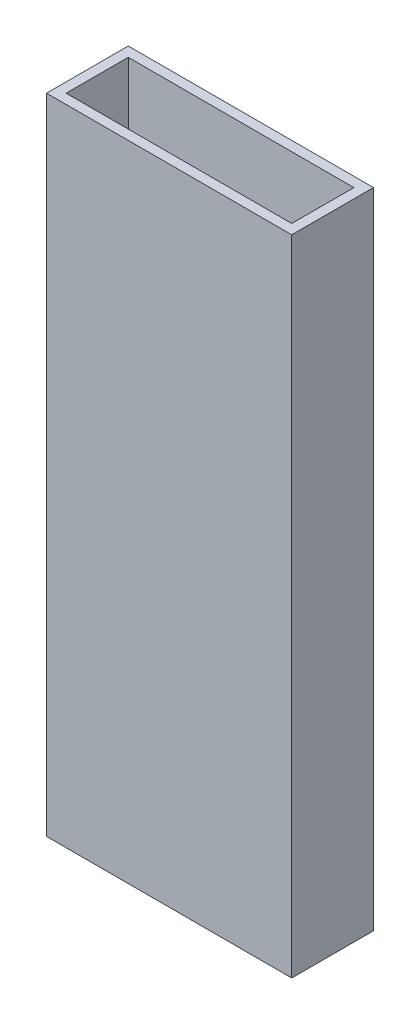
SolidWorks part; units mm, degrees
ref_plane "Front Plane" through (0, 0, 0) normal (0, 0, 1) x (1, 0, 0)
ref_plane "Top Plane" through (0, 0, 0) normal (0, 1, 0) x (1, 0, 0)
ref_plane "Right Plane" through (0, 0, 0) normal (1, 0, 0) x (0, 0, -1)
sketch "Sketch1" plane through (0, 0, 0) normal (0, 1, 0) x (1, 0, 0)
  line L0 (0, 9.652) -> (0, 12.7) construction
  line L1 (-38.1, 12.7) -> (38.1, 12.7)
  line L2 (-38.1, 12.7) -> (-38.1, -12.7)
  line L3 (-38.1, -12.7) -> (38.1, -12.7)
  line L4 (38.1, 12.7) -> (38.1, -12.7)
  line L5 (-35.052, 9.652) -> (35.052, 9.652)
  line L6 (-35.052, 9.652) -> (-35.052, -9.652)
  line L7 (-35.052, -9.652) -> (35.052, -9.652)
  line L8 (35.052, 9.652) -> (35.052, -9.652)
  line L9 (35.052, 0) -> (38.1, 0) construction
  line L10 (0, -9.652) -> (0, -12.7) construction
  line L11 (-35.052, 0) -> (-38.1, 0) construction
  line L12 (0, 9.652) -> (0, 0) construction
  line L13 (0, 0) -> (-35.052, 0) construction
  dimension "D1" = 76.2
  dimension "D2" = 25.4
  dimension "D3" = 3.048
extrude "Boss-Extrude1" add sketch "Sketch1" along normal blind 200
ref_plane "Plane1" through (0, 0, 0) normal (0, 0, 1) x (1, 0, 0)
sketch "Sketch2" plane through (0, 0, 0) normal (0, 0, 1) x (1, 0, 0)
  line L0 (0, 0) -> (0, 200) construction
  line L1 (-38.1, 200) -> (38.1, 200) construction
  line L2 (0, 100) -> (-38.1, 100) construction
  line L3 (-38.1, 200) -> (-38.1, 0) construction
  line L4 (0, 100) -> (38.1, 100) construction
  line L5 (38.1, 200) -> (38.1, 0) construction
ref_axis "Axis1" through (0, 200, 0) along (0, -1, 0)
equation "\"D1@Sketch1\" = 76.2'Length"
equation "\"D2@Sketch1\" = 25.4mm'Width"
equation "\"D3@Sketch1\"= 3.048 'Thickness"
